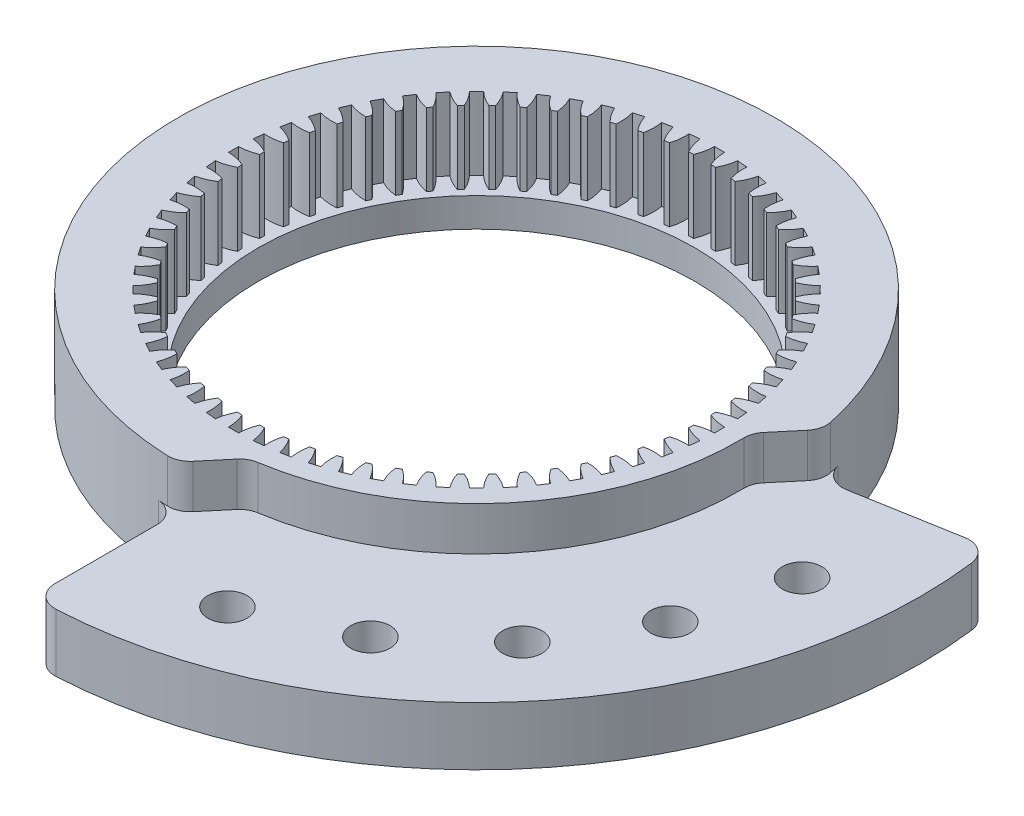
SolidWorks part; units mm, degrees
material "eSUN Tough Resin"
ref_plane "Front Plane" through (0, 0, 0) normal (0, 0, 1) x (1, 0, 0)
ref_plane "Top Plane" through (0, 0, 0) normal (0, 1, 0) x (1, 0, 0)
ref_plane "Right Plane" through (0, 0, 0) normal (1, 0, 0) x (0, 0, -1)
sketch "Sketch1" plane through (0, 0, 0) normal (0, 1, 0) x (1, 0, 0)
  circle A0 centre (0, 0) radius 16
  circle A1 centre (0, 0) radius 16.7
  circle A2 centre (0, 0) radius 15.5
  dimension "D1" = 32
  dimension "D2" = 33.4
  dimension "D3" = 1.2
extrude "Boss-Extrude1" add sketch "Sketch1" along normal mid plane 5 contours A1 A0 | A0 A2 | A2 region at (-15.5475, 0, 0) region at (-16.2277, 0, 0) region at (0, 0, 0)
sketch "Sketch7" plane through (0, 0, 0) normal (0, 1, 0) x (1, 0, 0)
  line L0 (16.7, 0) -> (-16.7, 0) construction
  line L1 (0, 16.7) -> (0, -16.7) construction
  circle A0 centre (0, 0) radius 16.7 construction
  point P7 (0, 0)
sketch "Sketch4" plane through (0, 0, 0) normal (0, 1, 0) x (1, 0, 0)
  line L0 (0, 0) -> (0, -30.5) construction
  line L10 (0, 0) -> (30.0366, 5.2963) construction
  line L11 (30.0366, 5.2963) -> (20.1886, 3.5598)
  line L12 (0, -30.5) -> (0, -20.5)
  circle A2 centre (0, 0) radius 15.5 construction
  circle A3 centre (0, 0) radius 15.5
  arc A4 (20.1886, 3.5598) -> (0, -20.5) centre (0, 0) ccw
  circle A9 centre (0, 0) radius 30.5 construction
  arc A10 (30.0366, 5.2963) -> (0, -30.5) centre (0, 0) cw
  dimension "D1" = 5
  dimension "D3" = 100
  dimension "D2" = 10
extrude "Boss-Extrude2" add sketch "Sketch4" along normal mid plane 5
sketch "Sketch3" plane through (0, 0, 0) normal (0, 1, 0) x (1, 0, 0)
  line L0 (0, 0) -> (0, 16.7) construction
  line L1 (-0.3927, 15.9952) -> (0.3927, 15.9952) construction
  line L2 (-0.3434, 15.4962) -> (0, 0) construction
  line L3 (0, 13.7683) -> (-0.5155, 16.692) construction
  line L4 (0, 0) -> (0.8194, 16.6799) construction
  line L5 (0.3927, 15.9952) -> (1.177, 15.9566) construction
  line L6 (0, 15.5) -> (0, 16.7) construction
  line L7 (0.3434, 15.4962) -> (0.3434, 16.7) construction
  line L8 (0.3434, 16.0981) -> (-0.3121, 16.0981) construction
  arc A1 (-0.5957, 16.6894) -> (-0.3434, 15.4962) centre (-3.6364, 15.4232) cw construction
  arc A2 (0.5957, 16.6894) -> (0.3434, 15.4962) centre (3.6364, 15.4232) ccw construction
  circle A3 centre (0, 0) radius 15.5 construction
  arc A4 (0.3434, 15.4962) -> (-0.3434, 15.4962) centre (0, 0) ccw construction
  circle A5 centre (0, 0) radius 16 construction
  circle A6 centre (0, 0) radius 16.7 construction
  arc A7 (0.5957, 15.5068) -> (-0.5957, 15.5068) centre (0, 32.1962) cw
  arc A8 (0.5957, 16.6894) -> (-0.5957, 16.6894) centre (0, 0) ccw construction
  arc A9 (-0.5957, 15.5068) -> (-0.3434, 16.7) centre (-3.6364, 16.773) ccw
  arc A10 (0.5957, 15.5068) -> (0.3434, 16.7) centre (3.6364, 16.773) cw
  arc A11 (0.3434, 16.7) -> (-0.3434, 16.7) centre (0, 32.1962) cw
  dimension "D3" = 2.813
  dimension "D2" = 10
extrude "Cut-Extrude1" cut sketch "Sketch3" against normal through all both and the other way through all
pattern_circular "CirPattern1" count 64 over 360 about axis through (0, 2.5, 0) along (0, 1, 0) of "Cut-Extrude1"
sketch "Sketch5" plane through (0, 0, 0) normal (0, 1, 0) x (1, 0, 0)
  circle A0 centre (0, 0) radius 15.5183
extrude "Cut-Extrude2" cut sketch "Sketch5" against normal through all both and the other way through all
sketch "Sketch8" plane through (0, -2.5, 0) normal (0, -1, 0) x (1, 0, 0)
  line L2 (0, 30.5) -> (0, 20.5)
  line L6 (0, 30.5) -> (0, 20.5)
  line L8 (20.1886, -3.5598) -> (30.0366, -5.2963)
  line L9 (20.1886, -3.5598) -> (30.0366, -5.2963)
  circle A0 centre (0, 0) radius 15
  arc A3 (30.0366, -5.2963) -> (0, 30.5) centre (0, 0) ccw
  arc A4 (30.0366, -5.2963) -> (0, 30.5) centre (0, 0) ccw
  arc A5 (0, 20.5) -> (20.1886, -3.5598) centre (0, 0) ccw
  arc A7 (0, 20.5) -> (20.1886, -3.5598) centre (0, 0) ccw
  dimension "D2" = 30
  dimension "D1" = 0
extrude "Boss-Extrude3" add sketch "Sketch8" along normal blind 2
sketch "Sketch6" plane through (0, 2.5, 0) normal (0, 1, 0) x (1, 0, 0)
  line L0 (0, 0) -> (7.3135, -24.4287) construction
  line L2 (0, -16.7) -> (0, 16.7) construction
  line L4 (0, -20.5) -> (0, -30.5) construction
  circle A3 centre (7.3135, -24.4287) radius 0.5
  point P5 (0, -25.5)
  point P11 (0, 0)
  dimension "D2" = 16.667
  dimension "D1" = 1
  dimension "D3" = 25.5
extrude "Cut-Extrude3" cut sketch "Sketch6" against normal through all
pattern_circular "CirPattern2" count 5 over 66.667 about axis through (0, -2.5, 0) along (0, -1, 0) of "Cut-Extrude3" reverse direction yes
sketch "Sketch9" plane through (0, 2.5, 0) normal (0, 1, 0) x (1, 0, 0)
  line L0 (20.1886, 3.5598) -> (17.9763, 0.9233)
  line L1 (0, -20.5) -> (2.2123, -17.8635)
  line L2 (0, 0) -> (16.4873, -13.8345) construction
  line L3 (2.2123, -17.8635) -> (17.9763, 0.9233) construction
  line L4 (20.1886, 3.5598) -> (30.0366, 5.2963)
  line L5 (0, -20.5) -> (0, -30.5)
  line L6 (0, 0) -> (135.2451, 0) construction
  line L7 (30.0366, 5.2963) -> (20.1886, 3.5598) construction
  arc A0 (2.2123, -17.8635) -> (17.9763, 0.9233) centre (0, 0) ccw
  arc A1 (0, -30.5) -> (30.0366, 5.2963) centre (0, 0) ccw construction
  arc A2 (0, -30.5) -> (30.0366, 5.2963) centre (0, 0) ccw
  point P5 (10.0943, -8.4701)
  dimension "D1" = 36
extrude "Cut-Extrude4" cut sketch "Sketch9" against normal offset from surface (3 mm away) 4 up to face at (14.1559, -4.5, 21.7839)
fillet "Fillet1" radius 1.5 6 edges at (20.1886, -2.5, -3.5598) (30.0366, -2.5, -5.2963) (0, -2.5, 30.5) (0, -2.5, 20.5) (17.9763, 1, -0.9233) (2.2123, 1, 17.8635)
fillet "Fillet2" radius 1.5 2 edges at (0, 1, 20.5) (20.1886, 1, -3.5598)
hole_wizard "CSK for M2.5 Countersunk Flat Head Screw1" positions "Sketch12" profile "Sketch11" countersink size "M2.5" standard "ISO"
sketch "Sketch12" plane through (0, -4.5, 0) normal (0, -1, 0) x (-1, 0, 0)
  point P0 (-7.3135, -24.4287)
  point P3 (-14.0125, -21.3049)
  point P6 (-19.5341, -16.3911)
  point P9 (-23.4145, -10.1)
  point P16 (-25.3276, -2.9604)
sketch "Sketch11" plane through (7.3135, -4.5, 24.4287) normal (1, 0, 0) x (0, 0, -1)
  line L0 (0, 0) -> (0, 4.8112)
  line L1 (0, 4.8112) -> (1.35, 4)
  line L2 (1.35, 4) -> (1.35, 1.4)
  line L3 (1.35, 1.4) -> (2.75, 0)
  line L5 (2.75, 0) -> (0, 0)
  line L6 (-1.35, 1.4) -> (-2.75, 0) construction
  line L10 (0, 4.8112) -> (-1.35, 4) construction
  line L11 (0, -6.35) -> (0, 107.95) construction
  dimension "Hole Dia." = 2.7
  dimension "Hole Depth" = 4
  dimension "Near C'Sink Dia." = 5.5
  dimension "Near C'Sink Angle" = 90
  dimension "Drill Angle" = 118
ref_axis "Axis2" through (0, -4.5, 0) along (0, 1, 0)
sketch "Sketch13" plane through (0, -4.5, 0) normal (0, -1, 0) x (1, 0, 0)
  line L0 (0, 0) -> (19.5341, 16.3911)
  point P0 (19.5341, 16.3911)
equation "\"Module\"= .5"
equation "\"Number of Teeth\"=64"
equation "\"D1@Sketch1\"=\"Module\"* \"Number of Teeth\""
equation "\"D2@Sketch1\"=(\"Number of Teeth\" + 2) * \"Module\" + .4"
equation "\"D3@Sketch1\"=\"Module\" * if( \"Module\" => 1.25, 2.25, 2.4)"
equation "\"D3@Sketch3\"=180 / \"Number of Teeth\""
equation "\"D1@CirPattern1\"=\"Number of Teeth\""
